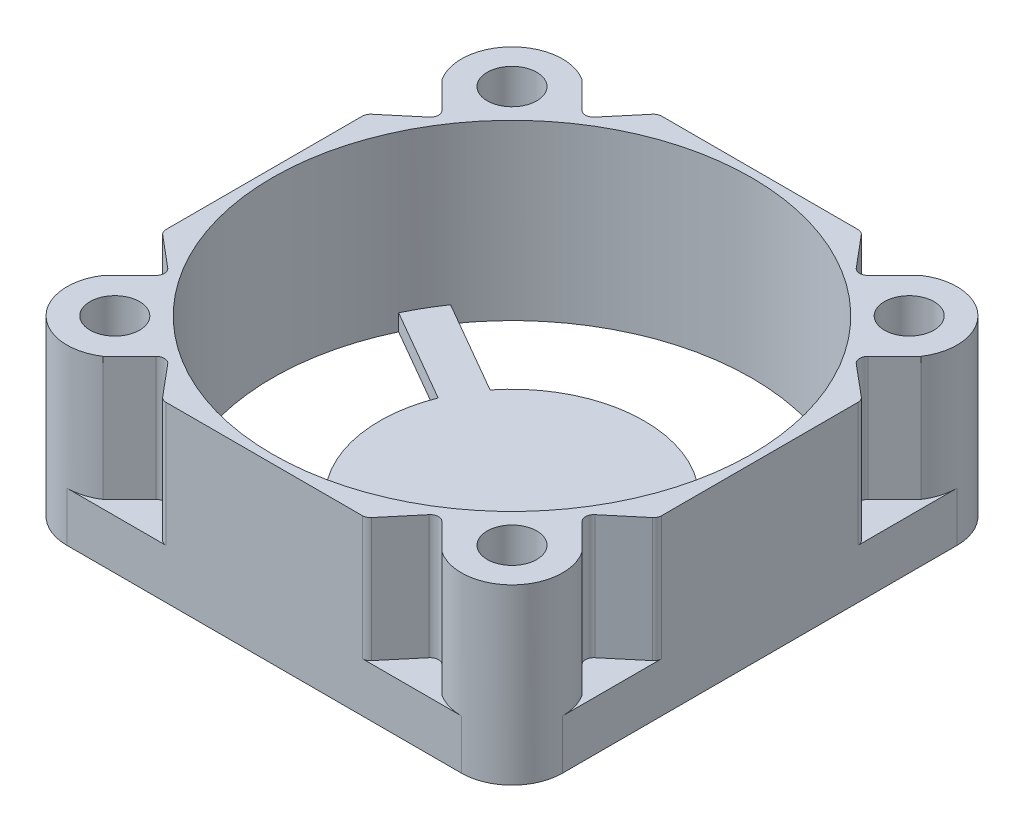
SolidWorks part; units mm, degrees
material "ABS"
ref_plane "Front Plane" through (0, 0, 0) normal (0, 0, 1) x (1, 0, 0)
ref_plane "Top Plane" through (0, 0, 0) normal (0, 1, 0) x (1, 0, 0)
ref_plane "Right Plane" through (0, 0, 0) normal (1, 0, 0) x (0, 0, -1)
sketch "Sketch2" plane through (0, 0, 0) normal (0, 1, 0) x (1, 0, 0)
  line L0 (-14.5, 0) -> (-15, 0) construction
  line L1 (15, 15) -> (-15, 15)
  line L2 (15, 15) -> (15, -15)
  line L3 (15, -15) -> (-15, -15)
  line L4 (-15, 15) -> (-15, -15)
  line L5 (15, 15) -> (-15, -15) construction
  line L6 (15, -15) -> (-15, 15) construction
  circle A0 centre (0, 0) radius 14.5
  point P0 (0, 0)
  dimension "D2" = 0.5
  dimension "D1" = 30
extrude "Boss-Extrude1" add sketch "Sketch2" along normal blind 10.5
sketch "Sketch3" plane through (0, 0, 0) normal (0, -1, 0) x (1, 0, 0)
  line L0 (0, 8) -> (0, 14.5) construction
  line L1 (1.15, 11.25) -> (-1.15, 11.25) construction
  line L2 (-1.15, 11.25) -> (-1.15, 14.4543)
  line L3 (1.15, 11.25) -> (1.15, 14.4543)
  line L4 (-1.15, 11.25) -> (-1.15, 7.9169)
  line L5 (1.15, 11.25) -> (1.15, 7.9169)
  line L6 (10.3178, -4.6291) -> (13.0928, -6.2312)
  line L7 (10.3178, -4.6291) -> (7.4312, -2.9625)
  line L8 (9.1678, -6.6209) -> (11.9428, -8.2231)
  line L9 (9.1678, -6.6209) -> (6.2812, -4.9544)
  line L10 (-9.1678, -6.6209) -> (-11.9428, -8.2231)
  line L11 (-9.1678, -6.6209) -> (-6.2812, -4.9544)
  line L12 (-10.3178, -4.6291) -> (-13.0928, -6.2312)
  line L13 (-10.3178, -4.6291) -> (-7.4312, -2.9625)
  circle A0 centre (0, 0) radius 8
  circle A1 centre (0, 0) radius 14.5 construction
  point P11 (0, 11.25)
  circle M7 centre (0, 0) radius 14.5
  dimension "D1" = 16
  dimension "D2" = 2.3
  dimension "D3" = 3
extrude "Boss-Extrude2" add sketch "Sketch3" against normal blind 1 contours A0 L5 L3 L2 L4 M7 | A0 | A0 L9 L8 L6 L7 M7 | A0 L13 L12 L10 L11 M7 region at (0, 0, 11.2285) region at (0, 0, 0) region at (-9.7242, 0, -5.6143) region at (9.7242, 0, -5.6143)
sketch "Sketch4" plane through (0, 10.5, 0) normal (0, 1, 0) x (1, 0, 0)
  line L0 (-15, 15) -> (15, -15) construction
  line L1 (-15, -15) -> (15, 15) construction
  line L2 (-10.253, 10.253) -> (-10.9602, 10.9602) construction
  line L3 (-14.1421, 9.8995) -> (-9.8995, 14.1421) construction
  line L4 (-14.1421, 9.8995) -> (-14.4957, 10.253)
  line L5 (-12.5061, 8.2634) -> (-15, 6.1708)
  line L6 (-14.1421, 9.8995) -> (-12.1525, 7.9099)
  line L7 (-9.8995, 14.1421) -> (-10.253, 14.4957)
  line L8 (-15, 15) -> (-15, -15) construction
  line L9 (-9.8995, 14.1421) -> (-7.9099, 12.1525)
  line L10 (-14.1028, 14.1028) -> (-13.0815, 13.0815) construction
  line L11 (-8.2634, 12.5061) -> (-6.1708, 15)
  line L12 (15, 15) -> (-15, 15) construction
  line L13 (9.8995, 14.1421) -> (7.9099, 12.1525)
  line L14 (14.1421, 9.8995) -> (12.1525, 7.9099)
  line L15 (12.5061, 8.2634) -> (15, 6.1708)
  line L16 (8.2634, 12.5061) -> (6.1708, 15)
  line L17 (9.8995, 14.1421) -> (10.253, 14.4957)
  line L18 (14.1421, 9.8995) -> (14.4957, 10.253)
  line L19 (14.1421, -9.8995) -> (12.1525, -7.9099)
  line L20 (9.8995, -14.1421) -> (7.9099, -12.1525)
  line L21 (8.2634, -12.5061) -> (6.1708, -15)
  line L22 (12.5061, -8.2634) -> (15, -6.1708)
  line L23 (14.1421, -9.8995) -> (14.4957, -10.253)
  line L24 (9.8995, -14.1421) -> (10.253, -14.4957)
  line L25 (-9.8995, -14.1421) -> (-7.9099, -12.1525)
  line L26 (-14.1421, -9.8995) -> (-12.1525, -7.9099)
  line L27 (-12.5061, -8.2634) -> (-15, -6.1708)
  line L28 (-8.2634, -12.5061) -> (-6.1708, -15)
  line L29 (-9.8995, -14.1421) -> (-10.253, -14.4957)
  line L30 (-14.1421, -9.8995) -> (-14.4957, -10.253)
  line L31 (-15, -6.1708) -> (-15, 6.1708)
  line L32 (-6.1708, 15) -> (6.1708, 15)
  line L33 (-6.1708, -15) -> (6.1708, -15)
  line L34 (15, -6.1708) -> (15, 6.1708)
  circle A0 centre (0, 0) radius 14.5 construction
  circle A1 centre (0, 0) radius 14.5
  circle A2 centre (-12.0208, 12.0208) radius 1.5
  arc A3 (-14.4957, 10.253) -> (-10.253, 14.4957) centre (-11.9369, 11.9369) cw
  arc A4 (10.253, 14.4957) -> (14.4957, 10.253) centre (11.9369, 11.9369) cw
  circle A5 centre (12.0208, 12.0208) radius 1.5
  arc A6 (14.4957, -10.253) -> (10.253, -14.4957) centre (11.9369, -11.9369) cw
  circle A7 centre (12.0208, -12.0208) radius 1.5
  arc A8 (-10.253, -14.4957) -> (-14.4957, -10.253) centre (-11.9369, -11.9369) cw
  circle A9 centre (-12.0208, -12.0208) radius 1.5
  point P19 (-12.0208, 12.0208)
  line M11 (-15, 15) -> (-15, -15)
  line M12 (-15, -15) -> (15, -15)
  line M13 (15, -15) -> (15, 15)
  line M14 (15, 15) -> (-15, 15)
  dimension "D2" = 3
  dimension "D1" = 1
  dimension "D3" = 6
  dimension "D5" = 0.5
  dimension "D6" = 0.5
  dimension "D7" = 0.5
  dimension "D8" = 95
  dimension "D9" = 95
  dimension "D10" = 4
extrude "Cut-Extrude1" cut sketch "Sketch4" against normal through all contours A3 M11 M14 | A4 M14 M13 | A8 M12 M11 | A6 M13 M12 | A2 | A9 | A5 | A7 region at (-14.3158, 10.5, -14.3158) region at (-14.3158, 10.5, 14.3158) region at (14.3158, 10.5, -14.3158) region at (14.3158, 10.5, 14.3158) region at (-12.0208, 10.5, -12.0208) region at (12.0208, 10.5, -12.0208) region at (12.0208, 10.5, 12.0208) region at (-12.0208, 10.5, 12.0208)
extrude "Cut-Extrude2" cut sketch "Sketch4<3>" against normal blind 7.5 contours A3 L7 L9 L11 M14 | L4 A3 L5 L6 M11 | L17 A4 L16 L13 M14 | A4 L18 L14 L15 M13 | L29 A8 L28 L25 M12 | A8 L30 L26 L27 M11 | L23 A6 L22 L19 M13 | A6 L24 L20 L21 M12 region at (-14.1861, 10.5, -8.459) region at (-8.459, 10.5, -14.1861) region at (-14.1861, 10.5, 8.459) region at (8.459, 10.5, -14.1861) region at (-8.459, 10.5, 14.1861) region at (14.1861, 10.5, -8.459) region at (8.459, 10.5, 14.1861) region at (14.1861, 10.5, 8.459)
sketch "Sketch4<3>" plane through (0, 10.5, 0) normal (0, 1, 0) x (1, 0, 0) same geometry as "Sketch4"
fillet "Fillet1" radius 0.5 16 edges at (-6.1708, 6.75, -15) (-8.2634, 6.75, -12.5061) (6.1708, 6.75, -15) (8.2634, 6.75, -12.5061) (12.5061, 6.75, -8.2634) (15, 6.75, -6.1708) (15, 6.75, 6.1708) (12.5061, 6.75, 8.2634) (-12.5061, 6.75, -8.2634) (-15, 6.75, -6.1708) (-15, 6.75, 6.1708) (-12.5061, 6.75, 8.2634) (8.2634, 6.75, 12.5061) (6.1708, 6.75, 15) (-6.1708, 6.75, 15) (-8.2634, 6.75, 12.5061)
